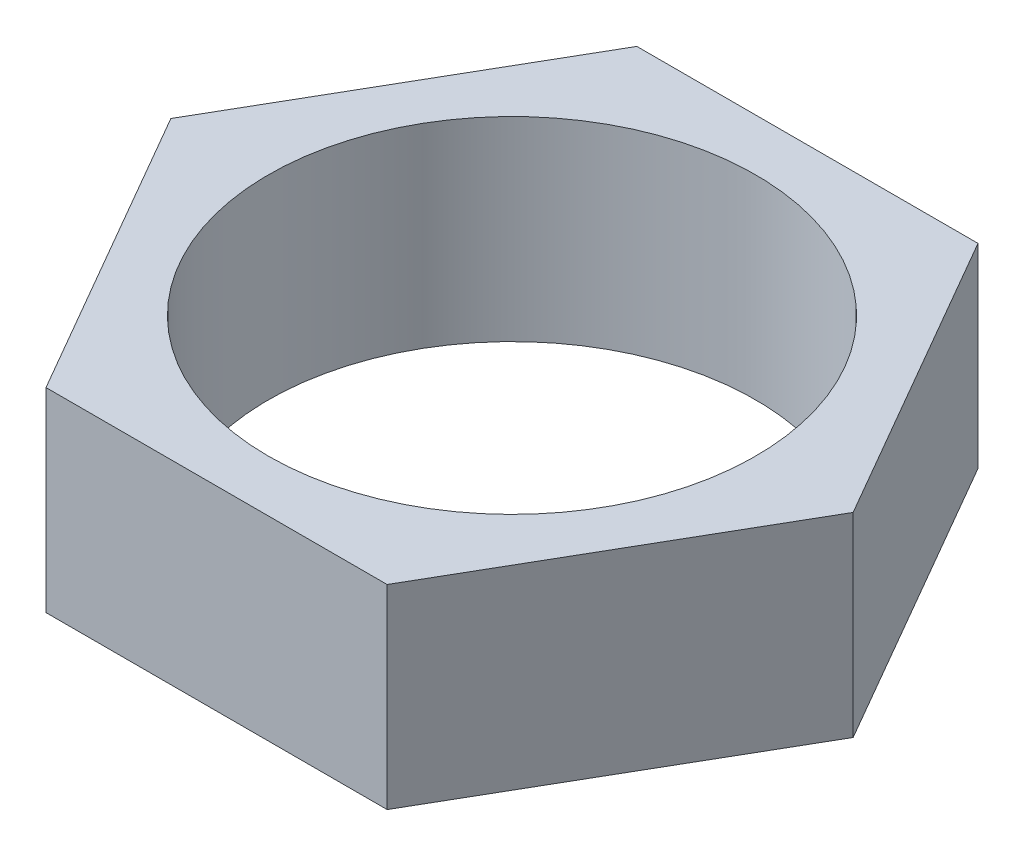
SolidWorks part; units mm, degrees
ref_plane "Front Plane" through (0, 0, 0) normal (0, 0, 1) x (1, 0, 0)
ref_plane "Top Plane" through (0, 0, 0) normal (0, 1, 0) x (1, 0, 0)
ref_plane "Right Plane" through (0, 0, 0) normal (1, 0, 0) x (0, 0, -1)
sketch "Sketch1" plane through (0, 0, 0) normal (0, 1, 0) x (1, 0, 0)
  line L1 (-17.5, 0) -> (-8.75, -15.1554)
  line L2 (-8.75, -15.1554) -> (8.75, -15.1554)
  line L3 (8.75, -15.1554) -> (17.5, 0)
  line L4 (17.5, 0) -> (8.75, 15.1554)
  line L5 (8.75, 15.1554) -> (-8.75, 15.1554)
  line L6 (-8.75, 15.1554) -> (-17.5, 0)
  circle A0 centre (0, 0) radius 17.5 construction
  circle A1 centre (0, 0) radius 12.5
  dimension "D1" = 35
  dimension "D2" = 25
extrude "Boss-Extrude1" add sketch "Sketch1" along normal blind 10
